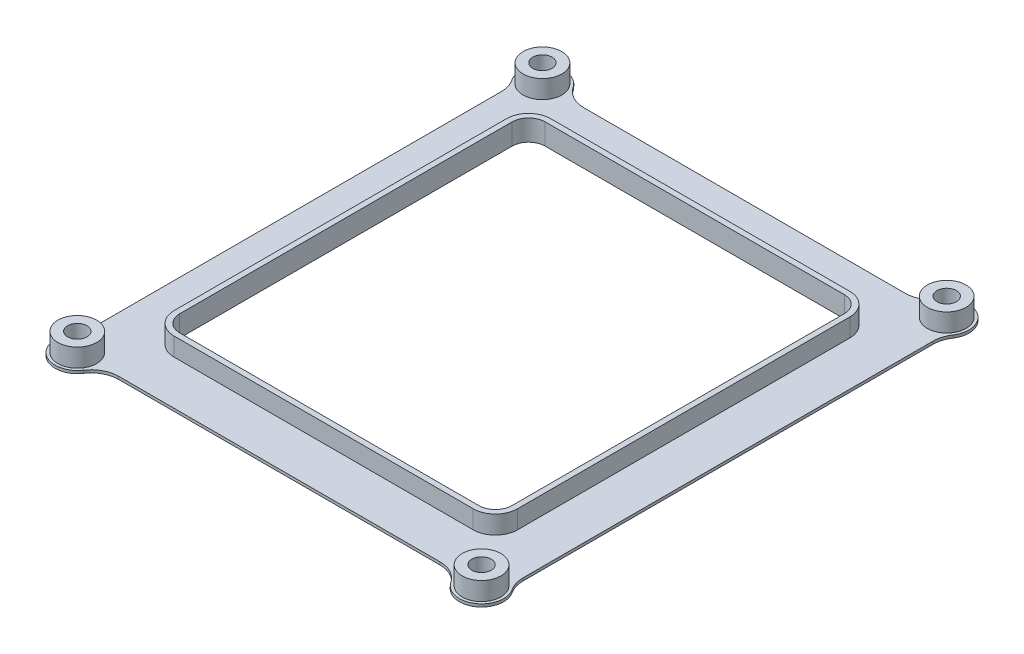
SolidWorks part; units mm, degrees
material "6061-T6 (SS)"
ref_plane "Front Plane" through (0, 0, 0) normal (0, 0, 1) x (1, 0, 0)
ref_plane "Top Plane" through (0, 0, 0) normal (0, 1, 0) x (1, 0, 0)
ref_plane "Right Plane" through (0, 0, 0) normal (1, 0, 0) x (0, 0, -1)
sketch "Sketch1" plane through (0, 0, 0) normal (0, 1, 0) x (1, 0, 0)
  line L0 (-33, 42) -> (33, 42)
  line L1 (-36.5, -42) -> (36.5, -42) construction
  line L2 (-36.5, -42) -> (-36.5, 42) construction
  line L3 (-36.5, 42) -> (36.5, 42) construction
  line L4 (36.5, -42) -> (36.5, 42) construction
  line L5 (-36.5, -42) -> (36.5, 42) construction
  line L6 (-36.5, 42) -> (36.5, -42) construction
  line L7 (36.5, 38.5) -> (36.5, -38.5)
  line L8 (33, -42) -> (-33, -42)
  line L9 (-36.5, -38.5) -> (-36.5, 38.5)
  line L11 (35.5, -41) -> (-35.5, -41)
  line L12 (35.5, -41) -> (35.5, 41)
  line L13 (35.5, 41) -> (-35.5, 41)
  line L14 (-35.5, -41) -> (-35.5, 41)
  line L15 (35.5, -41) -> (-35.5, 41) construction
  line L16 (35.5, 41) -> (-35.5, -41) construction
  circle A0 centre (-36.5, 42) radius 1.75
  circle A1 centre (36.5, 42) radius 1.75
  circle A2 centre (36.5, -42) radius 1.75
  circle A3 centre (-36.5, -42) radius 1.75
  circle A4 centre (-36.5, -42) radius 3.5
  circle A5 centre (-36.5, 42) radius 3.5
  circle A6 centre (36.5, 42) radius 3.5
  circle A7 centre (36.5, -42) radius 3.5
  point P0 (0, 0)
  point P22 (0, 0)
  dimension "D3" = 3.5
  dimension "D4" = 7
  dimension "D1" = 84
  dimension "D2" = 73
  dimension "D5" = 1
  dimension "D6" = 1
extrude "FrameAndBoltHoles" add sketch "Sketch1" along normal blind 3.8 contours A6 L0 A5 L13 | A5 L14 A0 L13 | L14 A5 L13 A0 | A5 L9 A4 L14 | A4 L11 A3 L14 | L11 A4 L14 A3 | A7 L11 A4 L8 | L12 A7 L11 A2 | A7 L12 A2 L11 | A7 L7 A6 L12 | L13 A6 L12 A1 | A6 L13 A1 L12 region at (-33.1346, 0, -41.509) region at (0, 0, -41.4996) region at (36.5, 0, -45.401) region at (-35.9997, 0, 0) region at (-34.5625, 0, -40.0625) region at (34.5625, 0, -40.0625) region at (-36.009, 0, 38.6346) region at (35.9997, 0, 0) region at (0, 0, 41.4996) region at (-34.5625, 0, 40.0625) region at (38.9049, 0, 39.5951) region at (34.5625, 0, 40.0625)
sketch "Sketch2" plane through (0, 0, 0) normal (0, 1, 0) x (1, 0, 0)
  line L0 (-35.5, -38.6459) -> (-35.5, 38.6459) construction
  line L1 (33.1459, 41) -> (-33.1459, 41) construction
  line L2 (-35.5, -38.6459) -> (-35.5, 38.6459)
  line L3 (33.1459, 41) -> (-33.1459, 41)
  circle A0 centre (-31, 36.5) radius 4.5
  arc A1 (-35.5, 38.6459) -> (-33.1459, 41) centre (-36.5, 42) ccw construction
  arc A2 (-35.5, 38.6459) -> (-33.1459, 41) centre (-36.5, 42) ccw
  dimension "D1" = 9
extrude "InsideFillet" add sketch "Sketch2" along normal up to surface (3.8 mm away) contours A2 L2 A0 L3 region at (-35.2954, 0, -38.216) up to face at (0, 3.8, 0)
mirror "MirrorFillet" about plane through (0, 0, 0) normal (1, 0, 0) of "InsideFillet"
mirror "MirrorFillet2" about plane through (0, 0, 0) normal (0, 0, 1) of "MirrorFillet"
sketch "Sketch3" plane through (0, 0, 0) normal (0, 1, 0) x (1, 0, 0)
  line L0 (-27, 41) -> (-27, 30)
  line L1 (33.1459, 41) -> (-33.1459, 41) construction
  line L2 (-27, 30) -> (-35.5, 30)
  line L3 (-35.5, -36.5) -> (-35.5, 36.5) construction
  line L4 (-35.5, -36.5) -> (-35.5, 36.5)
  line L5 (33.1459, 41) -> (-31, 41)
  line L6 (-27, 33) -> (-19, 41)
  line L7 (33.1459, 41) -> (-33.1459, 41) construction
  line L8 (-30, 30) -> (-35.5, 24.5)
  line L9 (-27, 30) -> (27, 30) construction
  line L11 (-27, 30) -> (-27, -30) construction
  line L13 (27, 30) -> (35.5, 30) construction
  line L14 (35.5, -36.5) -> (35.5, 36.5) construction
  line L15 (-27, -30) -> (-27, -41) construction
  line L16 (33.1459, -41) -> (-33.1459, -41) construction
  circle A0 centre (-27, 30) radius 4
  circle A1 centre (-27, 30) radius 3
  arc A3 (-31, 41) -> (-35.5, 36.5) centre (-31, 36.5) ccw
  point P8 (-27, 34)
  point P9 (-31, 30)
  point P16 (27, 30)
  dimension "D1" = 54
  dimension "D3" = 8
  dimension "D4" = 6
  dimension "D2" = 60
  dimension "D5" = 45
  dimension "D6" = 45
extrude "WireTrough" add sketch "Sketch3" along normal blind 0.5 contours A0 L6 L5 L0 | L5 A3 L4 L2 A0 L0 | A0 L2 L4 L8 | L6 A0 L0 | A1 L0 A0 L2 | L2 A0 L8 region at (-29.2433, 0, -32.2433) region at (-26.6957, 0, -33.6435) region at (-31.4847, 0, -35.8688) region at (-24.2985, 0, -38.4024) region at (-30.6435, 0, -29.6957) region at (-33.7624, 0, -28.1182)
sketch "Sketch4" plane through (0, 0.5, 0) normal (0, 1, 0) x (1, 0, 0)
  line L0 (-27, 33) -> (-19, 41) construction
  line L1 (-30, 30) -> (-35.5, 24.5) construction
  line L2 (-27, 33) -> (-19, 41)
  line L3 (-30, 30) -> (-35.5, 24.5)
  line L4 (0, 41) -> (0, 0) construction
  line L5 (0, 0) -> (-35.5, 0) construction
  line L6 (-35.5, -36.5) -> (-35.5, 24.5) construction
  line L7 (33.1459, 41) -> (-19, 41) construction
  line L8 (-27, 33) -> (0, 33)
  line L9 (0, 33) -> (0, 34)
  line L10 (0, 34) -> (-27, 34)
  line L11 (-30, 30) -> (-30, 0)
  line L12 (-31, 30) -> (-31, 0)
  line L13 (-31, 0) -> (-30, 0)
  line L14 (-27, 33) -> (-30, 30)
  circle A1 centre (-27, 30) radius 4
  arc A3 (-27, 33) -> (-30, 30) centre (-27, 30) ccw construction
  arc A4 (-27, 33) -> (-30, 30) centre (-27, 30) ccw
  arc A5 (-27, 33) -> (-30, 30) centre (-27, 30) ccw
  line M3 (-35.5, 24.5) -> (-30, 30)
  arc M4 (-30, 30) -> (-27, 33) centre (-27, 30) cw
  line M5 (-27, 33) -> (-19, 41)
  dimension "D1" = 8
extrude "WireInsideWall" add sketch "Sketch4" along normal up to surface (3.3 mm away) contours A1 L3 M5 M4 | A1 L8 L9 L10 L2 | L8 A1 M5 | A1 L11 M3 | A1 L3 L12 L13 L11 | A1 L2 L10 | A1 L12 L3 region at (-29.1604, 0.5, -32.1604) region at (-25.7456, 0.5, -33.3224) region at (-26.2882, 0.5, -33.9689) region at (-12.5815, 0.5, -33.5062) region at (-30.3224, 0.5, -28.7456) region at (-30.5056, 0.5, -14.0809) region at (-30.9689, 0.5, -29.2882) up to face at (0, 3.8, 0)
mirror "WireSpaceMirror" about plane through (0, 0, 0) normal (1, 0, 0) of "WireInsideWall", "WireTrough"
mirror "WireSpaceMirror2" about plane through (0, 0, 0) normal (0, 0, 1) of "WireSpaceMirror"
ref_plane "Plane1" through (0, 1.05, 0) normal (0, 1, 0) x (1, 0, 0)
sketch "Sketch6" plane through (0, 1.05, 0) normal (0, 1, 0) x (1, 0, 0)
  line L0 (-27, 30) -> (-27, 41) construction
  line L1 (-19, 41) -> (-31, 41) construction
  line L2 (-27, 30) -> (-35.5, 30) construction
  line L3 (-37.5, 30) -> (-37.5, 0)
  line L4 (-35.5, 24.5) -> (-35.5, 36.5) construction
  line L5 (0, 41) -> (0, 0) construction
  line L6 (33.1459, 41) -> (-33.1459, 41) construction
  line L7 (0, 0) -> (-35.5, 0) construction
  line L9 (-35.5, -36.5) -> (-35.5, 36.5) construction
  line L10 (-27, 40.5) -> (0, 40.5)
  line L11 (-27, 36) -> (-27, 37) construction
  line L12 (0, 39.5) -> (-27, 39.5)
  line L13 (-27, 39.5) -> (-27, 37) construction
  line L14 (-27, 37) -> (0, 37)
  line L15 (-27, 39.5) -> (-27, 40.5) construction
  line L16 (0, 36) -> (-27, 36)
  line L17 (-27, 40.5) -> (-27, 41) construction
  line L18 (-27, 35.5) -> (-27, 36) construction
  line L19 (-36.5, 0) -> (-36.5, 30)
  line L20 (-34, 30) -> (-34, 0)
  line L21 (-33, 30) -> (-33, 0)
  arc A0 (-27, 40.5) -> (-37.5, 30) centre (-27, 30) ccw
  arc A1 (-27, 39.5) -> (-36.5, 30) centre (-27, 30) ccw
  arc A2 (-27, 37) -> (-34, 30) centre (-27, 30) ccw
  arc A3 (-27, 36) -> (-33, 30) centre (-27, 30) ccw
  dimension "D1" = 0.5
  dimension "D2" = 1
  dimension "D3" = 1
  dimension "D4" = 0.5
sketch "Sketch7" plane through (0, 0.5, 0) normal (0, -1, 0) x (1, 0, 0)
  line L0 (19, -41) -> (-19, -41) construction
  line L1 (-35.5, 41) -> (35.5, 41)
  line L2 (-35.5, 41) -> (-35.5, -41)
  line L3 (-35.5, -41) -> (35.5, -41)
  line L4 (35.5, 41) -> (35.5, -41)
  line L5 (-35.5, 41) -> (35.5, -41) construction
  line L6 (-35.5, -41) -> (35.5, 41) construction
  line L7 (-30, 33) -> (30, 33)
  line L8 (-30, 33) -> (-30, -33)
  line L9 (-30, -33) -> (30, -33)
  line L10 (30, 33) -> (30, -33)
  line L11 (-30, 33) -> (30, -33) construction
  line L12 (-30, -33) -> (30, 33) construction
  line L13 (35.5, 24.5) -> (35.5, -24.5) construction
  line L14 (-27, -33) -> (27, -33) construction
  line L15 (30, -30) -> (30, 30) construction
  circle A0 centre (36.5, -42) radius 1.75
  circle A1 centre (-36.5, -42) radius 1.75
  circle A2 centre (-36.5, 42) radius 1.75
  circle A3 centre (36.5, 42) radius 1.75
  circle A5 centre (36.5, 42) radius 1.75 construction
  circle A6 centre (-36.5, 42) radius 1.75 construction
  circle A7 centre (-36.5, -42) radius 1.75 construction
  circle A8 centre (36.5, -42) radius 1.75 construction
  point P0 (0, 0)
  point P6 (0, 0)
  line M13 (27, -33) -> (-27, -33)
  line M14 (-27, -33) -> (-26, -34)
  line M15 (-26, -34) -> (26, -34)
  line M16 (26, -34) -> (27, -33)
extrude "InnerRing" add sketch "Sketch7" along normal up to surface (0.5 mm away) contours M16 M13 M14 M15 | A3 L1 A2 L2 A1 L3 A0 L4 L7 L10 L9 L8 M16 M15 M14 region at (0, 0.5, 39.9153) region at (0, 0.5, -33.4969) up to face at (0, 0, 0)
sketch "Sketch8" plane through (0, 3.8, 0) normal (0, 1, 0) x (1, 0, 0)
  line L0 (-27, 34) -> (27, 34) construction
  line L1 (31, -34) -> (-31, -34)
  line L2 (31, -34) -> (31, 34)
  line L3 (31, 34) -> (-31, 34)
  line L4 (-31, -34) -> (-31, 34)
  line L5 (31, -34) -> (-31, 34) construction
  line L6 (31, 34) -> (-31, -34) construction
  line L7 (50, -50) -> (-50, -50)
  line L8 (50, -50) -> (50, 50)
  line L9 (50, 50) -> (-50, 50)
  line L10 (-50, -50) -> (-50, 50)
  line L11 (50, -50) -> (-50, 50) construction
  line L12 (50, 50) -> (-50, -50) construction
  line L13 (-31, 30) -> (-31, -30) construction
  circle A0 centre (-36.5, 42) radius 3.5
  circle A1 centre (36.5, 42) radius 3.5
  circle A2 centre (36.5, -42) radius 3.5
  circle A3 centre (-36.5, -42) radius 3.5
  point P16 (0, 0)
  point P22 (0, 0)
  dimension "D1" = 100
  dimension "D2" = 100
extrude "RemoveOuterRing" cut sketch "Sketch8" against normal up to surface (3.3 mm away) up to face at (0, 0.5, 0)
sketch "Sketch9" plane through (0, 0, 0) normal (0, -1, 0) x (1, 0, 0)
  line L0 (0, 0) -> (0, -33) construction
  line L1 (-27, -33) -> (27, -33) construction
  line L2 (0, -33) -> (0, -46)
  line L5 (-40.5, 0) -> (-31, 0)
  line L6 (-31, 0) -> (0, 0) construction
  line L7 (-31, -30) -> (-31, 30) construction
  line L8 (-36.5, -46) -> (0, -46)
  line L9 (-40.5, -42) -> (-40.5, 0)
  circle A0 centre (-36.5, -42) radius 4
  circle A1 centre (-36.5, -42) radius 3.5 construction
  line M24 (-36.5, 38.5) -> (-36.5, -38.5)
  arc M25 (-36.5, -38.5) -> (-33, -42) centre (-36.5, -42) ccw
  line M26 (-33, -42) -> (33, -42)
  dimension "D1" = 0.5
extrude "Boss-Extrude2" add sketch "Sketch9" against normal up to surface (0.5 mm away) contours A0 M26 M25 M24 region at (-33.7516, 0, -44.7484) up to face at (0, 0.5, 0)
mirror "Mirror1" about plane through (0, 0, 0) normal (1, 0, 0) of "Boss-Extrude2"
mirror "Mirror2" about plane through (0, 0, 0) normal (0, 0, 1) of "Mirror1"
sketch "Sketch10" plane through (0, 0.5, 0) normal (0, 1, 0) x (1, 0, 0)
  line L0 (36.5, 38) -> (36.5, -38) construction
  line L1 (36.5, -38.8775) -> (39, -38.8775)
  line L2 (36.5, -38.8775) -> (36.5, 39.5505)
  line L3 (36.5, 39.5505) -> (39, 39.5505)
  line L4 (39, -38.8775) -> (39, 39.5505)
  line L5 (-36.5, -39.5505) -> (-39, -39.5505)
  line L6 (-36.5, -39.5505) -> (-36.5, 39.5505)
  line L7 (-36.5, 39.5505) -> (-39, 39.5505)
  line L8 (-39, -39.5505) -> (-39, 39.5505)
  line L11 (-36.5, -38) -> (-36.5, 38) construction
  circle A1 centre (36.5, 42) radius 3.5 construction
  circle A3 centre (-36.5, 42) radius 3.5 construction
  arc A4 (32.5, -42) -> (36.5, -38) centre (36.5, -42) ccw construction
  circle A5 centre (-36.5, -42) radius 3.5 construction
  dimension "D1" = 2.5
  dimension "D2" = 2.5
extrude "Boss-Extrude3" add sketch "Sketch10" against normal up to surface (0.5 mm away) up to face at (0, 0, 0)
fillet "Fillet1" radius 5 8 edges at (-32.5, 0.25, -42) (32.5, 0.25, -42) (39, 0.25, -38.8775) (39, 0.25, 38.8775) (32.5, 0.25, 42) (-32.5, 0.25, 42) (-39, 0.25, 38.8775) (-39, 0.25, -38.8775)
